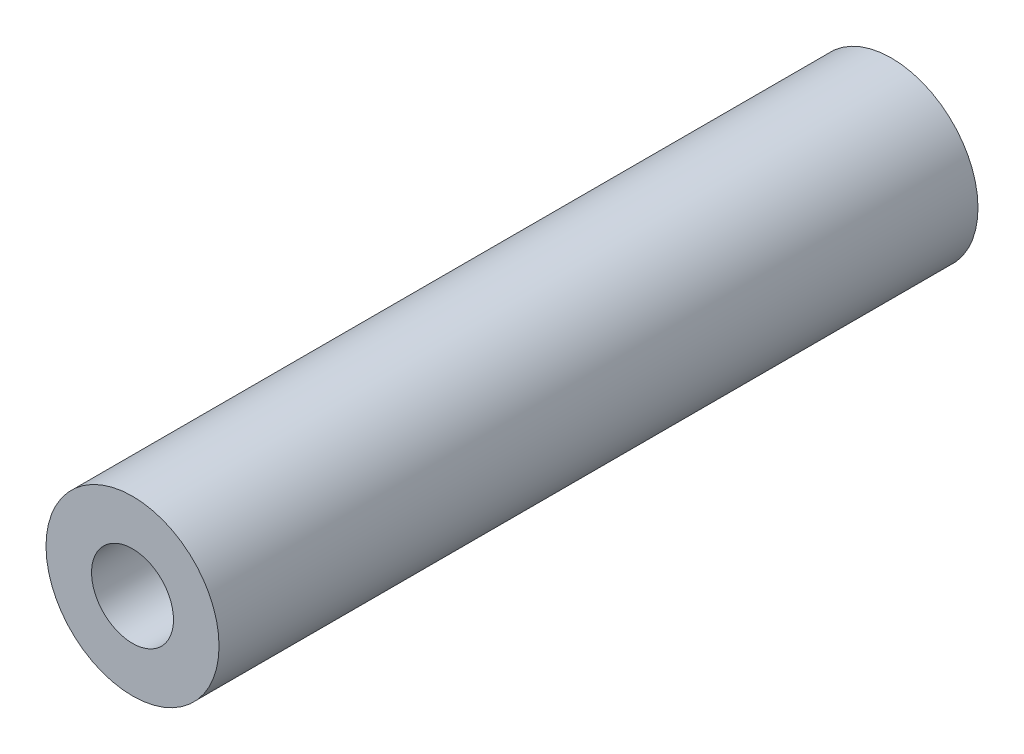
SolidWorks part; units mm, degrees
ref_plane "Front Plane" through (0, 0, 0) normal (0, 0, 1) x (1, 0, 0)
ref_plane "Top Plane" through (0, 0, 0) normal (0, 1, 0) x (1, 0, 0)
ref_plane "Right Plane" through (0, 0, 0) normal (1, 0, 0) x (0, 0, -1)
sketch "Sketch2" plane through (0, 0, 0) normal (0, 0, 1) x (1, 0, 0)
  circle A0 centre (0, 0) radius 2.7
  circle A1 centre (0, 0) radius 5.7
  dimension "D1" = 5.4
  dimension "D2" = 3
extrude "Boss-Extrude1" add sketch "Sketch2" along normal mid plane 50 contours A1 | A0
